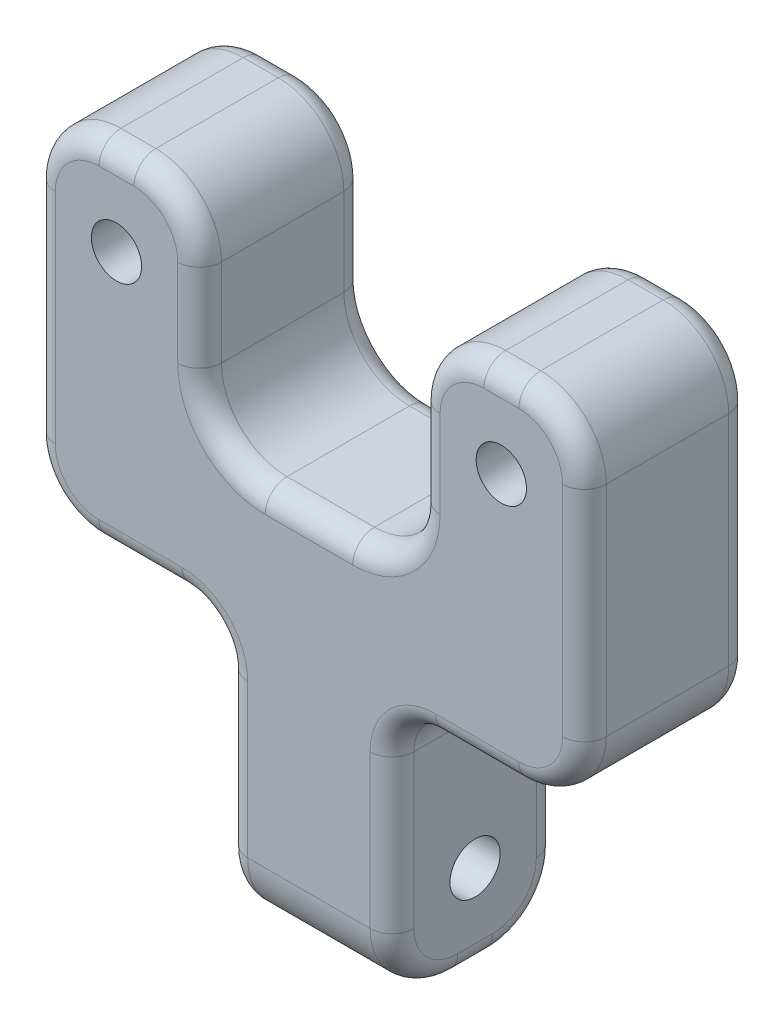
SolidWorks part; units mm, degrees
material "ABS"
ref_plane "Front Plane" through (0, 0, 0) normal (0, 0, 1) x (1, 0, 0)
ref_plane "Top Plane" through (0, 0, 0) normal (0, 1, 0) x (1, 0, 0)
ref_plane "Right Plane" through (0, 0, 0) normal (1, 0, 0) x (0, 0, -1)
sketch "Sketch1" plane through (0, 0, 0) normal (0, 0, 1) x (1, 0, 0)
  line L1 (-3.8, 6) -> (3.8, 6)
  line L2 (-3.8, 6) -> (-3.8, -6)
  line L3 (-3.8, -6) -> (3.8, -6)
  line L4 (3.8, 6) -> (3.8, -6)
  line L5 (-3.8, 6) -> (3.8, -6) construction
  line L6 (-3.8, -6) -> (3.8, 6) construction
  line L7 (-12.6, 6) -> (12.6, 6)
  line L8 (-12.6, 6) -> (-12.6, 22)
  line L9 (-12.6, 22) -> (12.6, 22)
  line L10 (12.6, 6) -> (12.6, 22)
  line L11 (-5, 22) -> (5, 22)
  line L12 (-5, 22) -> (-5, 12)
  line L13 (-5, 12) -> (5, 12)
  line L14 (5, 22) -> (5, 12)
  point P0 (0, 0)
  point P14 (0, 6)
  dimension "D1" = 10
  dimension "D2" = 12
  dimension "D3" = 7.6
  dimension "D4" = 7.6
  dimension "D5" = 7.6
  dimension "D6" = 10
  dimension "D7" = 6
extrude "Boss-Extrude1" add sketch "Sketch1" along normal blind 3.8 and the other way blind 3.8 contours L9 L14 L13 L12 L8 L7 L1 L10 | L4 L1 L2 L3 region at (-8.2, 6.2985, 0) region at (0, 0, 0)
sketch "Sketch2" plane through (3.8, 0, 0) normal (1, 0, 0) x (0, 0, -1)
  line L0 (-3.8, -6) -> (3.8, -6) construction
  circle A0 centre (0, -2) radius 1.15
  dimension "D1" = 2.3
  dimension "D2" = 4
extrude "Cut-Extrude1" cut sketch "Sketch2" against normal blind 7.6
sketch "Sketch3" plane through (0, 0, 3.8) normal (0, 0, 1) x (1, 0, 0)
  line L0 (-12.6, 22) -> (-5, 22) construction
  line L1 (-5, 22) -> (-5, 12) construction
  line L2 (0, -4.18) -> (0, 4.18) construction
  circle A0 centre (-8.8, 18) radius 1.15
  circle A1 centre (8.8, 18) radius 1.15
  dimension "D1" = 2.3
  dimension "D2" = 4
  dimension "D3" = 3.8
extrude "Cut-Extrude2" cut sketch "Sketch3" against normal blind 7.6
fillet "Fillet1" radius 3 6 edges at (0, -6, -3.8) (0, -6, 3.8) (12.6, 22, 0) (5, 22, 0) (-5, 22, 0) (-12.6, 22, 0)
fillet "Fillet2" radius 3 4 edges at (12.6, 6, 0) (-12.6, 6, 0) (5, 12, 0) (-5, 12, 0)
fillet "Fillet3" radius 2 2 edges at (3.8, 6, 0) (-3.8, 6, 0)
fillet "Fillet4" radius 1 48 edges at (-11.7213, 6.8787, 3.8) (-7.7, 6, 3.8) (-4.3858, 5.4142, 3.8) (-3.8, 0.5, 3.8) (-3.8, -5.1213, 2.9213) (-3.8, -6, 0) (-3.8, -5.1213, -2.9213) (-3.8, 0.5, -3.8) (-4.3858, 5.4142, -3.8) (-7.7, 6, -3.8) (-11.7213, 6.8787, -3.8) (-12.6, 14, -3.8) (-11.7213, 21.1213, -3.8) (-8.8, 22, -3.8) (-5.8787, 21.1213, -3.8) (-5, 17, -3.8) (-4.1213, 12.8787, -3.8) (0, 12, -3.8) (4.1213, 12.8787, -3.8) (5, 17, -3.8) (5.8787, 21.1213, -3.8) (8.8, 22, -3.8) (11.7213, 21.1213, -3.8) (12.6, 14, -3.8) (11.7213, 6.8787, -3.8) (7.7, 6, -3.8) (4.3858, 5.4142, -3.8) (3.8, 0.5, -3.8) (3.8, -5.1213, -2.9213) (3.8, -6, 0) (3.8, -5.1213, 2.9213) (3.8, 0.5, 3.8) (4.3858, 5.4142, 3.8) (7.7, 6, 3.8) (11.7213, 6.8787, 3.8) (12.6, 14, 3.8) (11.7213, 21.1213, 3.8) (8.8, 22, 3.8) (5.8787, 21.1213, 3.8) (5, 17, 3.8) (4.1213, 12.8787, 3.8) (0, 12, 3.8) (-4.1213, 12.8787, 3.8) (-5, 17, 3.8) (-5.8787, 21.1213, 3.8) (-8.8, 22, 3.8) (-11.7213, 21.1213, 3.8) (-12.6, 14, 3.8)
ref_axis "Axis1" through (-3.8, -2, 0) along (1, 0, 0)
ref_point "Point1"
ref_axis "Axis2" through (0, -2, 0) along (0, 1, 0)
